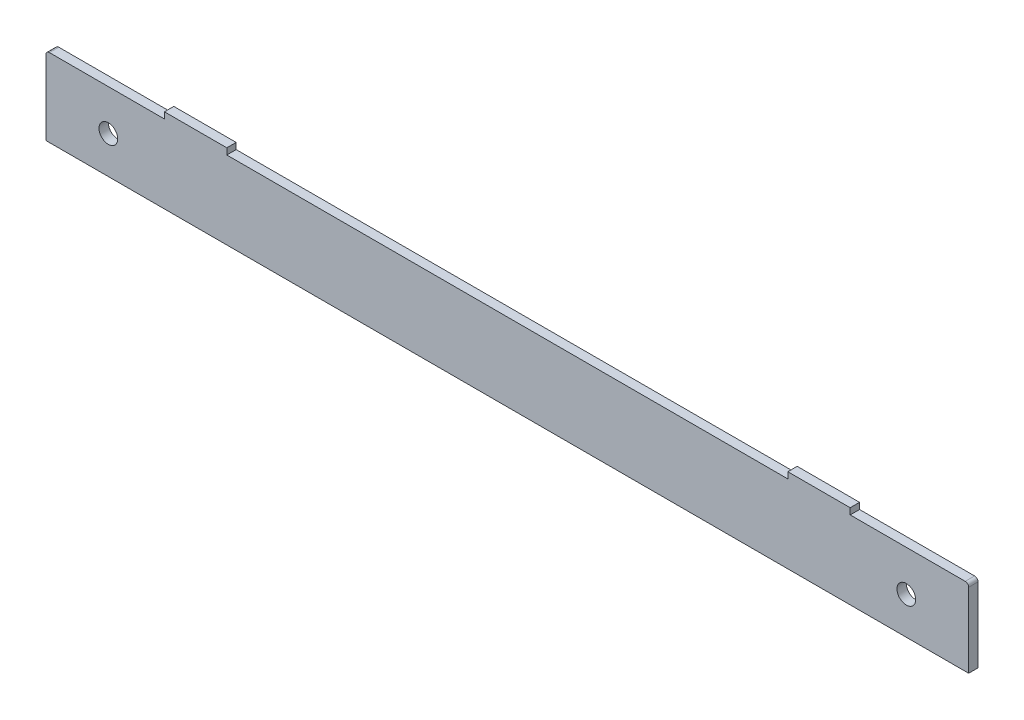
SolidWorks part; units mm, degrees
ref_plane "Спереди" through (0, 0, 0) normal (0, 0, 1) x (1, 0, 0)
ref_plane "Сверху" through (0, 0, 0) normal (0, 1, 0) x (1, 0, 0)
ref_plane "Справа" through (0, 0, 0) normal (1, 0, 0) x (0, 0, -1)
sketch "Эскиз1" plane through (0, 0, 0) normal (0, 0, 1) x (1, 0, 0)
  line L1 (-52.7153, 26.1806) -> (241.0847, 26.1806)
  line L2 (-53.8153, 25.0806) -> (-53.8153, 1.1806)
  line L3 (-53.8153, 1.1806) -> (242.1847, 1.1806)
  line L4 (242.1847, 25.0806) -> (242.1847, 1.1806)
  arc A0 (242.1847, 25.0806) -> (241.0847, 26.1806) centre (241.0847, 25.0806) ccw
  arc A1 (-53.8153, 25.0806) -> (-52.7153, 26.1806) centre (-52.7153, 25.0806) cw
  point P6 (242.1847, 26.1806)
  point P9 (-53.8153, 26.1806)
  dimension "D3" = 1.1
  dimension "D1" = 296
  dimension "D2" = 25
sheet metal parameters "Листовой металл1" thickness 3 parameters "D1"=1.1, "Толщина"=3
base flange "Базовая кромка1" sketch "Эскиз1" thickness 3 reverse thickness direction no parameters "D1"=1.1
sketch "Эскиз4" plane through (0, 26.1806, 0) normal (0, 1, 0) x (1, 0, 0)
  line L0 (94.1847, 3) -> (94.1847, 0) construction
  line L1 (241.0847, 3) -> (-52.7153, 3) construction
  line L2 (241.0847, 0) -> (-52.7153, 0) construction
  line L4 (-15.8153, 3) -> (4.1847, 3)
  line L5 (-15.8153, 3) -> (-15.8153, 0)
  line L6 (-15.8153, 0) -> (4.1847, 0)
  line L7 (4.1847, 3) -> (4.1847, 0)
  line L8 (184.1847, 3) -> (204.1847, 3)
  line L9 (184.1847, 3) -> (184.1847, 0)
  line L10 (184.1847, 0) -> (204.1847, 0)
  line L11 (204.1847, 3) -> (204.1847, 0)
  dimension "D1" = 20
  dimension "D2" = 20
  dimension "D3" = 90
  dimension "D4" = 90
extrude "Бобышка-Вытянуть1" add sketch "Эскиз4" along normal blind 2
sketch "Эскиз5" plane through (0, 0, -3) normal (0, 0, -1) x (-1, 0, 0)
  line L0 (-242.1847, 13.1306) -> (53.8153, 13.1306) construction
  line L1 (-242.1847, 1.1806) -> (-242.1847, 25.0806) construction
  line L2 (53.8153, 25.0806) -> (53.8153, 1.1806) construction
  line L3 (53.8153, 13.1306) -> (-94.1847, 26.1806) construction
  line L4 (-184.1847, 26.1806) -> (-4.1847, 26.1806) construction
  line L5 (-94.1847, 26.1806) -> (-94.1847, 1.1806) construction
  line L6 (53.8153, 1.1806) -> (-242.1847, 1.1806) construction
  circle A0 centre (-222.1847, 13.1306) radius 3
  circle A1 centre (33.8153, 13.1306) radius 3
  dimension "D1" = 6
  dimension "D2" = 6
  dimension "D3" = 20
  dimension "D4" = 20
extrude "Вырез-Вытянуть1" cut sketch "Эскиз5" against normal blind 10 normal cut yes
flat pattern "Развертка1" [suppressed]
sketch "Сгиб-Линии1" plane through (0, 0, 0) normal (0, 1, 0) x (1, 0, 0)
sketch3d "Граничная рамка1" [suppressed]
  line L0 (1.1, 1.1, 0) -> (-494.9, 1.0995, 0) construction
  line L1 (1.1, -24.8995, 0) -> (-494.9, -24.9, 0) construction
  line L2 (1.1, 1.1, 0) -> (1.1, -24.8995, 0) construction
  line L3 (-494.9, 1.0995, 0) -> (-494.9, -24.9, 0) construction
